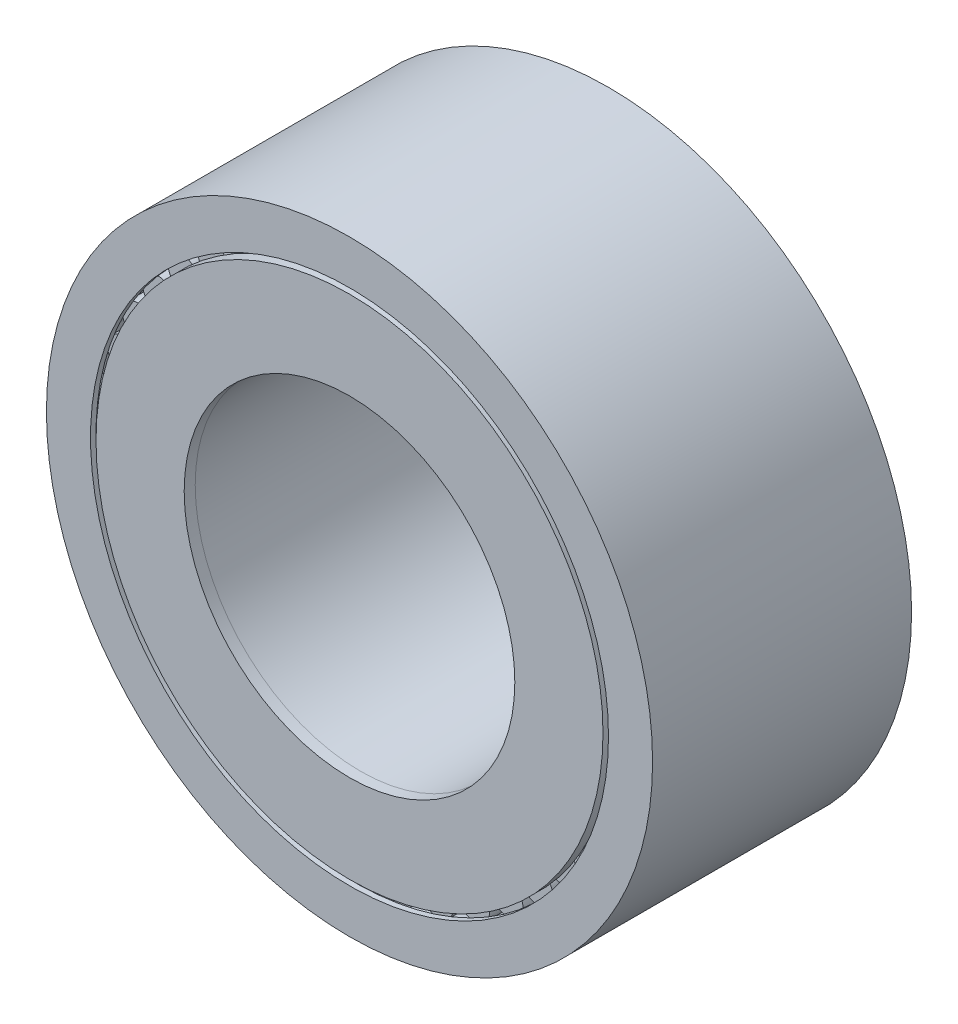
SolidWorks part; units mm, degrees
ref_plane "Alzado" through (0, 0, 0) normal (0, 0, 1) x (1, 0, 0)
ref_plane "Planta" through (0, 0, 0) normal (0, 1, 0) x (1, 0, 0)
ref_plane "Vista lateral" through (0, 0, 0) normal (1, 0, 0) x (0, 0, -1)
sketch "Croquis1" plane through (0, 0, 0) normal (0, 0, 1) x (1, 0, 0)
  circle A0 centre (0, 0) radius 22
  circle A1 centre (0, 0) radius 15
  dimension "D1" = 44
  dimension "D2" = 30
extrude "Saliente-Extruir1" add sketch "Croquis1" along normal blind 20
sketch "Croquis2" plane through (0, 0, 20) normal (0, 0, 1) x (1, 0, 0)
  line L0 (0, 0) -> (0, 22.7) construction
  line L1 (0, 22) -> (0, 22.7) construction
  circle A0 centre (0, 22.7) radius 1.45
  circle A2 centre (0, 0) radius 22 construction
  point P3 (0, 22)
  dimension "D1" = 2.9
  dimension "D2" = 0.7
extrude "Cortar-Extruir1" cut sketch "Croquis2" against normal blind 23
pattern_circular "MatrizC1" count 40 over 360 about axis through (0, 0, 20) along (0, 0, 1) of "Cortar-Extruir1"
sketch "Croquis3" plane through (0, 0, 20) normal (0, 0, 1) x (1, 0, 0)
  circle A0 centre (-10.3056, 20.2258) radius 1.4
  dimension "D1" = 2.8
extrude "Saliente-Extruir2" add sketch "Croquis3" against normal up to surface (20 mm away) up to face at (0, 0, 0)
pattern_circular "MatrizC4" count 40 over 360 about axis through (0, 0, 20) along (0, 0, 1) of bodies 104
ref_plane "Plano1" through (0, 0, 10) normal (0, 0, -1) x (-1, 0, 0)
sketch "Croquis4" plane through (0, 0, 20) normal (0, 0, 1) x (1, 0, 0)
  circle A0 centre (0, 0) radius 24.1
  circle A1 centre (0, 0) radius 27.5
  circle A2 centre (22.4205, -3.5511) radius 1.4 construction
  dimension "D1" = 55
extrude "Saliente-Extruir3" add sketch "Croquis4" against normal up to surface (20 mm away) separate body up to face at (0, 0, 0)
sketch "Croquis5" plane through (0, 0, 0) normal (0, 0, -1) x (-1, 0, 0)
  circle A0 centre (0, 0) radius 15
  circle A1 centre (0, 0) radius 23
  dimension "D1" = 30
  dimension "D2" = 46
extrude "Saliente-Extruir4" add sketch "Croquis5" along normal blind 3.5
sketch "Croquis6" plane through (0, 0, 0) normal (0, 0, -1) x (-1, 0, 0)
  circle A0 centre (0, 0) radius 27.5
  circle A2 centre (0, 0) radius 24.1 construction
  circle A3 centre (0, 0) radius 24.1
  dimension "D2" = 55
extrude "Saliente-Extruir7" add sketch "Croquis6" along normal blind 1
sketch "Croquis7" plane through (0, 0, -1) normal (0, 0, -1) x (-1, 0, 0)
  circle A0 centre (0, 0) radius 27.5 construction
  circle A1 centre (0, 0) radius 27.5
  circle A2 centre (0, 0) radius 23.5
  dimension "D1" = 47
extrude "Saliente-Extruir8" add sketch "Croquis7" along normal blind 2.5
sketch "Croquis8" plane through (0, 0, 20) normal (0, 0, 1) x (1, 0, 0)
  circle A1 centre (0, 22.7) radius 1.4
  circle A2 centre (0, 22.7) radius 1.4
  dimension "D1" = 0
extrude "Cortar-Extruir2" cut sketch "Croquis8" against normal blind 1
pattern_circular "MatrizC5" count 40 over 360 about axis through (0, 0, 20) along (0, 0, -1) of "Cortar-Extruir2"
sketch "Croquis9" plane through (0, 0, 20) normal (0, 0, 1) x (1, 0, 0)
  circle A0 centre (0, 0) radius 24.1 construction
  circle A1 centre (0, 0) radius 24.1
  circle A2 centre (0, 0) radius 23.5
  dimension "D1" = 47
extrude "Saliente-Extruir10" add sketch "Croquis9" against normal blind 0.5
sketch "Croquis10" plane through (0, 0, 20) normal (0, 0, 1) x (1, 0, 0)
  circle A2 centre (0, 0) radius 15 construction
  circle A3 centre (0, 0) radius 23
  circle A4 centre (0, 0) radius 23
  circle A5 centre (0, 0) radius 15
  dimension "D1" = 0
extrude "Saliente-Extruir11" add sketch "Croquis10" against normal blind 1 separate body
sketch "Croquis11" plane through (0, 0, 20) normal (0, 0, 1) x (1, 0, 0)
  circle A0 centre (0, 0) radius 22.4027
extrude "Cortar-Extruir3" cut sketch "Croquis11" against normal blind 1
sketch "Croquis12" plane through (0, 0, -3.5) normal (0, 0, -1) x (-1, 0, 0)
  line L0 (0, 0) -> (0, 10) construction
  line L1 (0, 0) -> (10, 0) construction
  circle A0 centre (0, 10) radius 4
  circle A2 centre (0, 0) radius 23
  circle A3 centre (0, 0) radius 3.8
  circle A4 centre (9.5106, 3.0902) radius 4
  circle A5 centre (5.8779, -8.0902) radius 4
  circle A6 centre (-5.8779, -8.0902) radius 4
  circle A7 centre (-9.5106, 3.0902) radius 4
  point P18 (0, 0)
  dimension "D1" = 8
  dimension "D2" = 10
  dimension "D3" = 7.6
  dimension "D5" = 46
  dimension "D4" = 5
extrude "Saliente-Extruir12" add sketch "Croquis12" along normal blind 1
chamfer "Chaflán1" distance 1 angle 45 1 edges at (-23, 0, -4.5)
chamfer "Chaflán2" distance 1 angle 45 5 edges at (-13.5106, 3.0902, -4.5) (-9.8779, -8.0902, -4.5) (1.8779, -8.0902, -4.5) (5.5106, 3.0902, -4.5) (-4, 10, -4.5)
